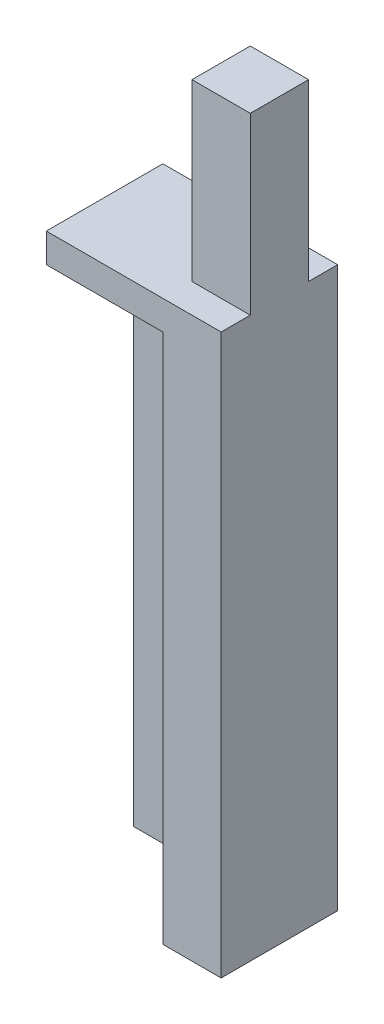
SolidWorks part; units mm, degrees
ref_plane "Front Plane" through (0, 0, 0) normal (0, 0, 1) x (1, 0, 0)
ref_plane "Top Plane" through (0, 0, 0) normal (0, 1, 0) x (1, 0, 0)
ref_plane "Right Plane" through (0, 0, 0) normal (1, 0, 0) x (0, 0, -1)
sketch "Sketch3" plane through (0, 0, 0) normal (0, 0, 1) x (1, 0, 0)
  line L0 (0, 0) -> (0, -5)
  line L1 (0, -5) -> (20, -5)
  line L2 (20, -5) -> (20, -25)
  line L3 (0, 0) -> (20, 0)
  line L4 (20, 0) -> (20, 30)
  line L5 (20, 30) -> (30, 30)
  line L6 (30, 30) -> (30, -25)
  line L7 (30, -25) -> (20, -25)
  dimension "D1" = 20
  dimension "D2" = 20
  dimension "D3" = 20
  dimension "D4" = 5
  dimension "D5" = 10
  dimension "D6" = 55
extrude "Boss-Extrude3" add sketch "Sketch3" along normal blind 10
sketch "Sketch4" plane through (0, 0, 0) normal (0, 0, -1) x (-1, 0, 0)
  line L5 (0, 0) -> (-30, 0)
  line L6 (0, 0) -> (0, -25)
  line L7 (0, -25) -> (-30, -25)
  line L8 (-30, 0) -> (-30, -25)
extrude "Boss-Extrude4" add sketch "Sketch4" along normal blind 5
sketch "Sketch5" plane through (0, 0, 10) normal (0, 0, 1) x (1, 0, 0)
  line L0 (0, 0) -> (0, -5)
  line L1 (0, -5) -> (20, -5)
  line L2 (20, -5) -> (20, -25)
  line L3 (20, -25) -> (30, -25)
  line L4 (30, -25) -> (30, 0)
  line L5 (30, 0) -> (0, 0)
extrude "Boss-Extrude5" add sketch "Sketch5" along normal blind 5
sketch "Sketch6" plane through (0, -25, 0) normal (0, -1, 0) x (1, 0, 0)
  line L0 (20, 15) -> (20, 0)
  line L1 (20, 0) -> (30, 0) construction
  line L2 (20, 0) -> (0, 0)
  line L3 (0, 0) -> (0, -5)
  line L4 (0, -5) -> (30, -5)
  line L5 (30, -5) -> (30, 15)
  line L6 (30, 15) -> (20, 15)
extrude "Boss-Extrude6" add sketch "Sketch6" along normal up to surface (71 mm away)
